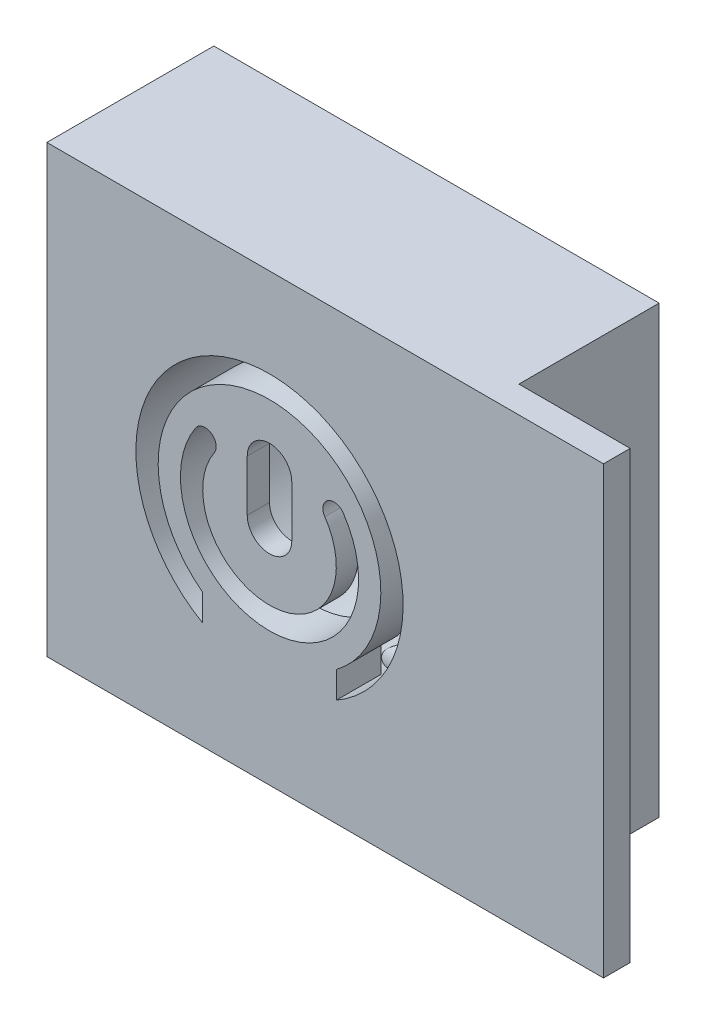
SolidWorks part; units mm, degrees
material "ABS"
ref_plane "Front Plane" through (0, 0, 0) normal (0, 0, 1) x (1, 0, 0)
ref_plane "Top Plane" through (0, 0, 0) normal (0, 1, 0) x (1, 0, 0)
ref_plane "Right Plane" through (0, 0, 0) normal (1, 0, 0) x (0, 0, -1)
sketch "Sketch1" plane through (0, 0, 0) normal (0, 0, 1) x (1, 0, 0)
  line L1 (-10, 10) -> (10, 10)
  line L2 (-10, 10) -> (-10, -10)
  line L3 (-10, -10) -> (10, -10)
  line L4 (10, 10) -> (10, -10)
  line L5 (-10, 10) -> (10, -10) construction
  line L6 (-10, -10) -> (10, 10) construction
  point P0 (0, 0)
  dimension "D1" = 20
  dimension "D2" = 20
extrude "Boss-Extrude1" add sketch "Sketch1" along normal blind 7.5
sketch "Sketch2" plane through (0, 0, 0) normal (0, 0, -1) x (-1, 0, 0)
  circle A0 centre (0, 0) radius 6
  dimension "D1" = 12
extrude "Cut-Extrude1" cut sketch "Sketch2" against normal blind 5.5
sketch "Sketch3" plane through (0, 0, 5.5) normal (0, 0, -1) x (-1, 0, 0)
  line L0 (-3, -4) -> (-3, -5.1962)
  line L1 (0, 6) -> (0, -6) construction
  line L2 (3, -4) -> (3, -5.1962)
  arc A0 (3, -5.1962) -> (-3, -5.1962) centre (0, 0) ccw
  circle A1 centre (0, 0) radius 5
  circle A2 centre (0, 0) radius 6 construction
  circle M5 centre (0, 0) radius 6
  dimension "D1" = 10
  dimension "D2" = 3
extrude "Cut-Extrude2" cut sketch "Sketch3" against normal blind 5 contours L1 A0 L0 A1 | L1 A1 L2 M5 region at (3.127, -4.5981, 5.5) region at (-0.127, 5.5, 5.5)
sketch "Sketch4" plane through (0, 0, 5.5) normal (0, 0, -1) x (-1, 0, 0)
  circle A0 centre (0, 0) radius 4
  dimension "D1" = 8
extrude "Cut-Extrude3" cut sketch "Sketch4" against normal blind 1
sketch "Sketch5" plane through (0, 0, 7.5) normal (0, 0, 1) x (1, 0, 0)
  line L0 (0, 2.3) -> (0, 0) construction
  line L1 (-1, 2.3) -> (-1, 0)
  line L2 (1, 2.3) -> (1, 0)
  arc A0 (-1, 2.3) -> (1, 2.3) centre (0, 2.3) cw
  arc A1 (-1, 0) -> (1, 0) centre (0, 0) ccw
  arc A2 (-2.4828, 1.684) -> (2.4828, 1.684) centre (0, 0) ccw
  arc A3 (-3.3104, 2.2453) -> (3.3104, 2.2453) centre (0, 0) ccw
  arc A4 (-2.4828, 1.684) -> (-3.3104, 2.2453) centre (-2.8966, 1.9647) ccw
  arc A5 (2.4828, 1.684) -> (3.3104, 2.2453) centre (2.8966, 1.9647) cw
  point P10 (0, 0)
  dimension "D4" = 3
  dimension "D5" = 2.3
  dimension "D1" = 1
  dimension "D2" = 1
  dimension "D3" = 1
extrude "Cut-Extrude4" cut sketch "Sketch5" against normal up to next
sketch "Sketch6" plane through (0, 0, 0) normal (0, 0, -1) x (-1, 0, 0)
  line L0 (0, 10) -> (0, -10) construction
  line L1 (6.5, 2.75) -> (8.5, 2.75)
  line L2 (6.5, 2.75) -> (6.5, -2.75)
  line L3 (6.5, -2.75) -> (8.5, -2.75)
  line L4 (8.5, 2.75) -> (8.5, -2.75)
  line L5 (6.5, 2.75) -> (8.5, -2.75) construction
  line L6 (6.5, -2.75) -> (8.5, 2.75) construction
  line L7 (-2.75, -6.5) -> (2.75, -6.5)
  line L8 (-2.75, -6.5) -> (-2.75, -8.5)
  line L9 (-2.75, -8.5) -> (2.75, -8.5)
  line L10 (2.75, -6.5) -> (2.75, -8.5)
  line L11 (-2.75, -6.5) -> (2.75, -8.5) construction
  line L12 (-2.75, -8.5) -> (2.75, -6.5) construction
  line L13 (-10, 10) -> (10, 10) construction
  line L14 (10, -10) -> (-10, -10) construction
  line L15 (-10, 0) -> (10, 0) construction
  line L16 (-10, -10) -> (-10, 10) construction
  line L17 (10, 10) -> (10, -10) construction
  point P0 (7.5, 0)
  point P5 (0, -7.5)
  dimension "D1" = 2
  dimension "D2" = 5.5
  dimension "D3" = 1.5
  dimension "D4" = 1.5
extrude "Cut-Extrude5" cut sketch "Sketch6" against normal blind 7
sketch "Sketch7" plane through (-10, 0, 0) normal (-1, 0, 0) x (0, 0, 1)
  line L0 (0, 0) -> (7.5, 0) construction
  line L1 (7.5, 10) -> (7.5, -10) construction
  circle A0 centre (3.75, 0) radius 1.5
  dimension "D1" = 3
extrude "Cut-Extrude6" cut sketch "Sketch7" against normal up to next
sketch "Sketch8" plane through (0, -10, 0) normal (0, -1, 0) x (-1, 0, 0)
  line L0 (0, -7.5) -> (0, 0) construction
  line L1 (10, -7.5) -> (-10, -7.5) construction
  line L2 (10, 0) -> (-10, 0) construction
  circle A0 centre (0, -3.75) radius 1.5
  dimension "D1" = 3
extrude "Cut-Extrude7" cut sketch "Sketch8" against normal up to next
sketch "Sketch9" plane through (10, 0, 0) normal (1, 0, 0) x (0, 0, -1)
  line L0 (0, 0) -> (-7.5, 0) construction
  line L1 (-7.5, -10) -> (-7.5, 10) construction
  line L2 (-3.75, 10) -> (-3.75, 0) construction
  line L3 (-7.5, 10) -> (0, 10) construction
  circle A0 centre (-3.75, 4) radius 1.8
  circle A1 centre (-3.75, -4) radius 1.8
  dimension "D1" = 3.6
  dimension "D2" = 4
extrude "Cut-Extrude8" cut sketch "Sketch9" against normal up to next
sketch "Sketch10" plane through (10, 0, 0) normal (1, 0, 0) x (0, 0, -1)
  line L0 (-7.5, -10) -> (0, -10) construction
  line L1 (-7.5, 10) -> (-6.3, 10)
  line L2 (-7.5, 10) -> (-7.5, -10)
  line L3 (-7.5, -10) -> (-6.3, -10)
  line L4 (-6.3, 10) -> (-6.3, -10)
  dimension "D1" = 1.2
extrude "Boss-Extrude2" add sketch "Sketch10" along normal blind 5
sketch "Sketch11" plane through (0, 0, 5.5) normal (0, 0, -1) x (-1, 0, 0)
  line L0 (0, 0) -> (0, 4.5) construction
  circle A0 centre (0, 4.5) radius 0.5
  arc A1 (3, -4) -> (-3, -4) centre (0, 0) ccw construction
  circle A2 centre (0, 0) radius 4 construction
extrude "Boss-Extrude3" add sketch "Sketch11" along normal blind 2
sketch "Sketch12" plane through (0, 0, 0) normal (0, 0, -1) x (-1, 0, 0)
  line L0 (0, 0) -> (0, 4.5) construction
  line L18 (-3.33, 6.575) -> (3.33, 6.575)
  line L19 (-3.33, 6.575) -> (-3.33, 2.425)
  line L20 (-3.33, 2.425) -> (3.33, 2.425)
  line L21 (3.33, 6.575) -> (3.33, 2.425)
  line L22 (-3.33, 6.575) -> (3.33, 2.425) construction
  line L23 (-3.33, 2.425) -> (3.33, 6.575) construction
  dimension "D1" = 6.66
  dimension "D2" = 4.15
extrude "Cut-Extrude9" cut sketch "Sketch12" against normal up to surface (3.5 mm away) up to face at (-0.5, 4.5, 3.5)
sketch "Sketch13" plane through (0, 0, 0) normal (0, 0, -1) x (-1, 0, 0)
  line L0 (3.33, 6.575) -> (3.33, 4.9911) construction
  line L1 (-3.33, 6.575) -> (3.33, 6.575)
  line L2 (-3.33, 6.575) -> (-3.33, 2.425)
  line L3 (-3.33, 2.425) -> (3.33, 2.425)
  line L4 (3.33, 6.575) -> (3.33, 2.425)
  line L5 (-5.33, 0.425) -> (5.33, 0.425)
  line L6 (5.33, 8.575) -> (5.33, 0.425)
  line L7 (-5.33, 8.575) -> (5.33, 8.575)
  line L8 (-5.33, 8.575) -> (-5.33, 0.425)
  dimension "D1" = 4.15
  dimension "D2" = 2
extrude "Boss-Extrude4" add sketch "Sketch13" along direction (0, 0, -1) on the side against the normal blind 2.5
